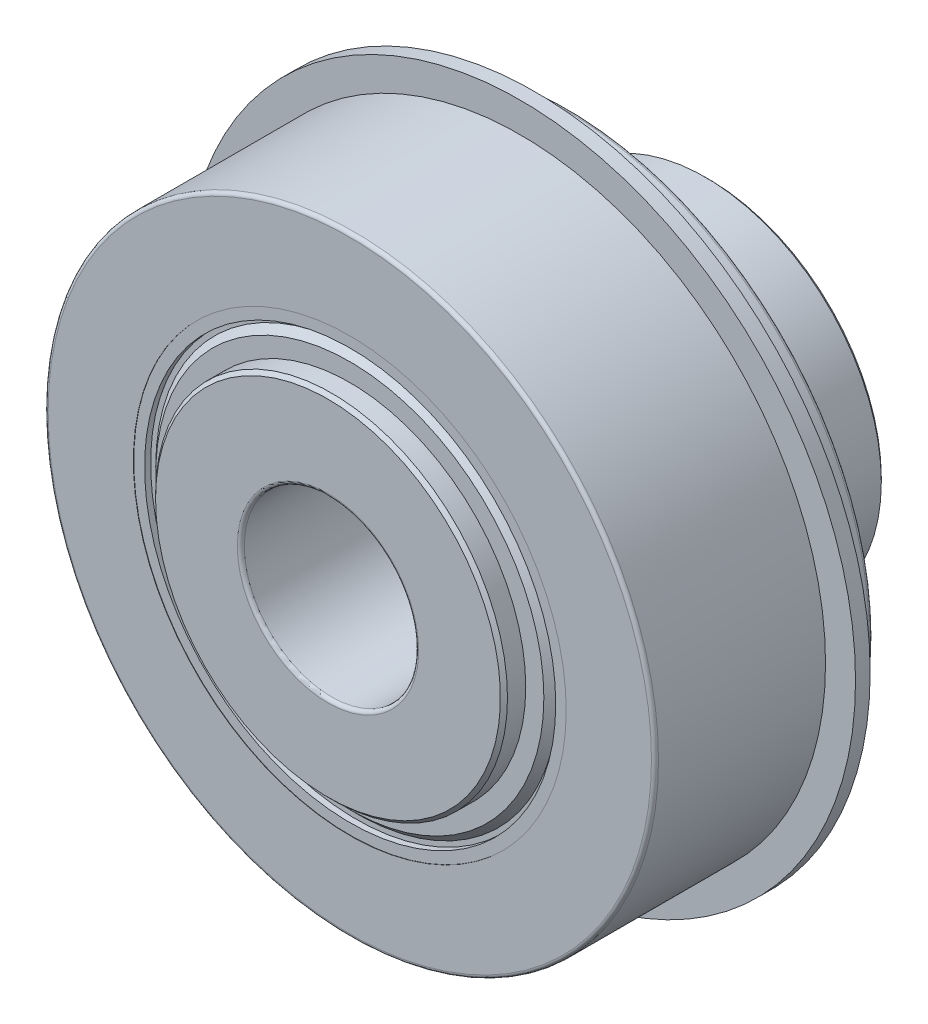
SolidWorks part; units mm, degrees
note: '?' marks a value the reader was unsure of.
ref_plane "Front Plane" through (0, 0, 0) normal (0, 0, 1) x (1, 0, 0)
ref_plane "Top Plane" through (0, 0, 0) normal (0, 1, 0) x (1, 0, 0)
ref_plane "Right Plane" through (0, 0, 0) normal (1, 0, 0) x (0, 0, -1)
sketch "Sketch1" plane through (0, 0, 0) normal (1, 0, 0) x (0, 0, -1)
  line L0 (-9.525, 0) -> (9.525, 0) construction
  line L1 (0, 0) -> (0, 22.225) construction
  line L2 (-3.6852, 15.7607) -> (3.6852, 15.7607) construction
  line L3 (-9.525, 12.8143) -> (18.2118, 12.8143) construction
  line L4 (-9.525, 12.8143) -> (-9.525, 6.35)
  line L5 (-9.525, 6.35) -> (18.2118, 6.35)
  line L7 (-7.9375, 15.7607) -> (7.9375, 15.7607) construction
  line L8 (-7.9375, 15.7607) -> (-7.9375, 22.225) construction
  line L9 (-7.9375, 22.225) -> (7.9375, 22.225) construction
  line L10 (7.9375, 15.7607) -> (7.9375, 22.225) construction
  line L11 (-3.6852, 12.8143) -> (3.6852, 12.8143) construction
  line L12 (0, 18.2562) -> (0, 22.225) construction
  line L13 (4.4831, 21.5786) -> (5.5499, 21.5786) construction
  line L14 (4.4831, 21.5786) -> (4.4831, 24.4094) construction
  line L15 (4.4831, 24.4094) -> (5.5499, 24.4094) construction
  line L16 (5.5499, 21.5786) -> (5.5499, 24.4094) construction
  line L17 (0, 18.2562) -> (0, 14.2875) construction
  line L18 (3.6852, 12.8143) -> (18.2118, 12.8143)
  line L19 (-9.525, 12.8143) -> (-3.6852, 12.8143)
  line L20 (18.2118, 6.35) -> (18.2118, 12.8143)
  circle A0 centre (0, 14.2875) radius 3.9688 construction
  arc A1 (-3.6852, 12.8143) -> (3.6852, 12.8143) centre (0, 14.2875) ccw
  point P5 (0, 6.35)
  dimension "D1" = 9.525
  dimension "OD" = 44.45
  dimension "Shaft Dia" = 12.7
  dimension "F" = 25.6286
  dimension "A" = 1.5875
  dimension "D2" = 0.6464
  dimension "H" = 1.0668
  dimension "D3" = 6.4643
  dimension "P" = 48.8188
  dimension "B" = 15.875
  dimension "overall" = 27.7368
  dimension "G" = 3.4544
revolve "Revolve1" add sketch "Sketch1" angle 360 about L0
sketch "Sketch3" plane through (0, 0, 0) normal (1, 0, 0) x (0, 0, -1)
  line L0 (-3.6852, 15.7607) -> (-7.9375, 15.7607)
  line L1 (-7.9375, 15.7607) -> (-7.9375, 22.225)
  line L2 (-7.9375, 22.225) -> (4.4831, 22.225)
  line L3 (-7.9375, 22.225) -> (7.9375, 22.225) construction
  line L4 (4.4831, 22.225) -> (4.4831, 21.5786)
  line L5 (4.4831, 21.5786) -> (5.5499, 21.5786)
  line L6 (5.5499, 21.5786) -> (5.5499, 22.225)
  line L7 (7.9375, 22.225) -> (7.9375, 15.7607)
  line L8 (7.9375, 15.7607) -> (3.6852, 15.7607)
  line L9 (5.5499, 22.225) -> (7.9375, 22.225)
  arc A0 (-3.6852, 15.7607) -> (3.6852, 15.7607) centre (0, 14.2875) cw
revolve "Revolve2" add sketch "Sketch3" angle 360 about L0
sketch "Sketch4" plane through (0, 0, 0) normal (1, 0, 0) x (0, 0, -1)
  line L1 (4.4831, 24.4094) -> (5.5499, 24.4094)
  line L2 (4.4831, 24.4094) -> (4.4831, 21.5786)
  line L3 (4.4831, 21.5786) -> (5.5499, 21.5786)
  line L4 (5.5499, 24.4094) -> (5.5499, 21.5786)
revolve "Revolve3" add sketch "Sketch4" angle 360 about L0
sketch "Sketch5" plane through (0, 0, 0) normal (1, 0, 0) x (0, 0, -1)
  line L0 (-7.9375, 14.133) -> (-7.9375, 12.8143)
  line L1 (-9.525, 12.8143) -> (-3.6852, 12.8143) construction
  line L2 (-7.9375, 22.225) -> (-7.9375, -22.225) construction
  line L3 (-7.9375, 14.133) -> (-7.4459, 14.6246)
  line L4 (-7.4459, 14.6246) -> (-7.4459, 15.3199)
  line L5 (-7.4459, 15.3199) -> (-7.4713, 15.3199)
  line L6 (-7.4713, 15.3199) -> (-7.4713, 14.9722)
  line L7 (-7.4713, 14.9722) -> (-7.9121, 14.9722)
  line L8 (-7.9121, 14.9722) -> (-7.9121, 15.7607)
  line L9 (-7.9375, 15.7607) -> (7.9375, 15.7607) construction
  line L10 (-7.9121, 15.7607) -> (-7.005, 15.7607)
  line L11 (-7.005, 15.7607) -> (-7.005, 14.442)
  line L12 (-7.005, 14.442) -> (-7.4967, 13.9504)
  line L13 (-7.4967, 13.9504) -> (-7.4967, 12.8143)
  line L14 (-7.9375, 12.8143) -> (-7.4967, 12.8143)
  line L15 (0, 22.225) -> (0, 25.0558) construction
  line L16 (-7.9375, 22.225) -> (7.9375, 22.225) construction
  line L17 (-7.4586, 15.3199) -> (-7.4586, 15.7607) construction
  line L18 (-7.6917, 14.3788) -> (-7.38, 14.0671) construction
  line L19 (-7.4459, 14.9722) -> (-7.005, 14.9722) construction
  line L20 (-7.9121, 15.7607) -> (-7.9375, 15.7607) construction
  line L21 (7.9121, 15.7607) -> (7.9375, 15.7607) construction
  line L22 (7.4459, 14.9722) -> (7.005, 14.9722) construction
  line L23 (7.6917, 14.3788) -> (7.38, 14.0671) construction
  line L24 (7.4586, 15.3199) -> (7.4586, 15.7607) construction
  line L25 (7.9375, 12.8143) -> (7.4967, 12.8143)
  line L26 (7.4967, 13.9504) -> (7.4967, 12.8143)
  line L27 (7.005, 14.442) -> (7.4967, 13.9504)
  line L28 (7.005, 15.7607) -> (7.005, 14.442)
  line L29 (7.9121, 15.7607) -> (7.005, 15.7607)
  line L30 (7.9121, 14.9722) -> (7.9121, 15.7607)
  line L31 (7.4713, 14.9722) -> (7.9121, 14.9722)
  line L32 (7.4713, 15.3199) -> (7.4713, 14.9722)
  line L33 (7.4459, 15.3199) -> (7.4713, 15.3199)
  line L34 (7.4459, 14.6246) -> (7.4459, 15.3199)
  line L35 (7.9375, 14.133) -> (7.4459, 14.6246)
  line L36 (7.9375, 14.133) -> (7.9375, 12.8143)
  line L37 (4.4831, 21.5786) -> (4.4831, 24.4094) construction
  point P0 (-7.4459, 14.9722)
  dimension "D1" = 45
  dimension "D2" = 0.0254
revolve "Revolve4" add sketch "Sketch5" angle 360 about L0
sketch "Sketch7" plane through (0, 0, 0) normal (1, 0, 0) x (0, 0, -1)
  line L0 (3.6852, 12.8143) -> (18.2118, 12.8143) construction
  line L1 (12.2936, 12.8143) -> (14.7066, 12.8143)
  line L2 (12.2936, 12.8143) -> (12.2936, 0)
  line L3 (12.2936, 0) -> (14.7066, 0)
  line L4 (14.7066, 12.8143) -> (14.7066, 0)
  line L5 (-9.525, 0) -> (9.525, 0) construction
  line L6 (12.2936, 12.8143) -> (12.2936, 15.7607) construction
  line L7 (-7.9375, 15.7607) -> (7.9375, 15.7607) construction
  dimension "Screw Dia" = 4.826
  dimension "M" = 5.9182
revolve "Cut-Revolve2" cut sketch "Sketch7" angle 360 about L2
sketch "Sketch8" plane through (0, 0, 0) normal (1, 0, 0) x (0, 0, -1)
  line L0 (12.2936, 12.8143) -> (12.2936, 0) construction
  line L1 (12.2936, 6.9808) -> (14.7066, 6.9808)
  line L2 (12.2936, 6.9808) -> (12.2936, 13.3223)
  line L3 (12.2936, 13.3223) -> (14.7066, 13.3223)
  line L4 (14.7066, 6.9808) -> (14.7066, 13.3223)
  line L5 (14.7066, 12.8143) -> (14.7066, 0) construction
  line L7 (-9.525, 6.35) -> (18.2118, 6.35) construction
  dimension "D1" = 6.3415
  dimension "D2" = 0.6308
  dimension "D3" = 0.508
revolve "Revolve5" add sketch "Sketch8" angle 360 about L2
sketch "Sketch9" plane through (0, 13.3223, 0) normal (0, 1, 0) x (-1, 0, 0)
  line L0 (0, 9.525) -> (0, -18.2118) construction
  line L1 (0, -13.6867) -> (1.2065, -12.9902)
  line L2 (1.2065, -12.9902) -> (1.2065, -11.597)
  line L3 (1.2065, -11.597) -> (0, -10.9005)
  line L4 (0, -10.9005) -> (-1.2065, -11.597)
  line L5 (-1.2065, -11.597) -> (-1.2065, -12.9902)
  line L6 (-1.2065, -12.9902) -> (0, -13.6867)
  circle A0 centre (0, -12.2936) radius 1.2065 construction
  dimension "D1" = 2.413
extrude "Cut-Extrude1" cut sketch "Sketch9" against normal blind 1.5854
chamfer "Chamfer1" distance 0.2413 angle 45 1 edges at (0, 13.3223, -9.8806)
ref_axis "Axis1" through (0, 0, -9.525) along (0, 0, 1)?
pattern_circular "CirPattern1" count 2 every 120 about axis through (0, 0, -9.525) along (0, 0, 1) of "Cut-Revolve2"
pattern_circular "CirPattern2" count 2 every 120 about axis through (0, 0, 0) along (0, 0, 1) of bodies 355
chamfer "Chamfer2" distance 0.2563 angle 45 2 edges at (12.8143, 0, -18.2118) (12.8143, 0, 9.525)
fillet "Fillet1" radius 0.2563 2 edges at (6.35, 0, -18.2118) (6.35, 0, 9.525)
fillet "Fillet2" radius 0.2563 2 edges at (22.225, 0, -7.9375) (22.225, 0, 7.9375)
delete or keep bodies "Body-Delete1" [suppressed] type delete bodies bodies 349
equation "\"D2@Sketch1\" = \"D3@Sketch1\"*.1"
equation "\"D2@Sketch8\" = \"D1@Sketch8\"*.1"
equation "\"D1@Sketch9\" = \"Screw Dia@Sketch7\"/2"
equation "\"D1@Cut-Extrude1\" = \"D1@Sketch8\"/4"
equation "\"D1@Chamfer1\" = \"Screw Dia@Sketch7\"*.05"
equation "\"D1@Chamfer2\" = \"F@Sketch1\"*.01"
equation "\"D1@Fillet1\" = \"D1@Chamfer2\""
equation "\"D1@Fillet2\" = \"D1@Fillet1\""
equation "\"D1@Sketch1\" = \"B@Sketch1\"/2+\"A@Sketch1\""
